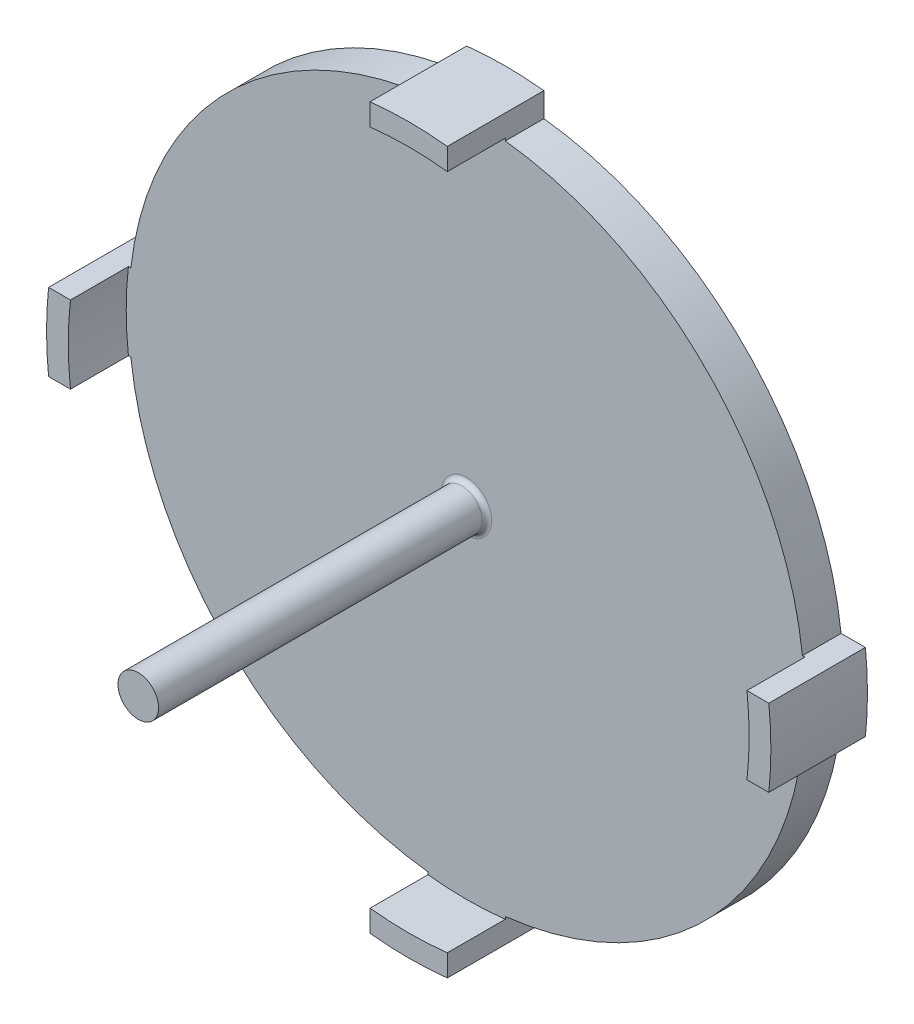
SolidWorks part; units mm, degrees
ref_plane "Front Plane" through (0, 0, 0) normal (0, 0, 1) x (1, 0, 0)
ref_plane "Top Plane" through (0, 0, 0) normal (0, 1, 0) x (1, 0, 0)
ref_plane "Right Plane" through (0, 0, 0) normal (1, 0, 0) x (0, 0, -1)
sketch "Sketch1" plane through (0, 0, 0) normal (0, 0, 1) x (1, 0, 0)
  line L0 (37.5, 4) -> (34.7707, 4)
  line L1 (-4, 37.5) -> (-4, 34.7707)
  line L2 (4, 37.5) -> (4, 34.7707)
  line L3 (4, -37.5) -> (4, -34.7707)
  line L4 (-37.5, -4) -> (-34.7707, -4)
  line L6 (4, 34.7707) -> (4, 37.5)
  line L8 (-34.7707, 4) -> (-37.5, 4)
  line L10 (-4, -34.7707) -> (-4, -37.5)
  line L12 (4, -34.7707) -> (4, -37.5)
  line L13 (34.7707, -4) -> (37.5, -4)
  circle A0 centre (0, 0) radius 35
  arc A1 (4, 35.0223) -> (-4, 35.0223) centre (0, 0) ccw
  arc A2 (-37.2861, 4) -> (-37.2861, -4) centre (0, 0) ccw
  arc A3 (-4, -37.2861) -> (4, -37.2861) centre (0, 0) ccw
  arc A4 (37.2861, -4) -> (37.2861, 4) centre (0, 0) ccw
  arc A5 (4, 37.2861) -> (-4, 37.2861) centre (0, 0) ccw
  arc A6 (-35.0223, 4) -> (-35.0223, -4) centre (0, 0) ccw
  arc A7 (35.0223, -4) -> (35.0223, 4) centre (0, 0) ccw
  arc A8 (-4, -35.0223) -> (4, -35.0223) centre (0, 0) ccw
  point P18 (0, 0)
  dimension "D1" = 70
  dimension "D2" = 70.5
  dimension "D3" = 75
  dimension "D4" = 4
extrude "Boss-Extrude1" add sketch "Sketch1" along normal blind 10 contours A6 L8 A2 L4 | L6 A5 L1 A1 | A7 L13 A4 L0 | A8 L10 A3 L12 region at (36.3014, 0, 0) region at (0, 36.3014, 0) region at (0, -36.3014, 0) region at (-36.3014, 0, 0)
extrude "Boss-Extrude2" add sketch "Sketch1<3>" along normal blind 4 contours A0 | L8 A6 L4 A0 | L10 A8 L3 A0 | L6 A1 L1 A0 | L13 A7 L0 A0 region at (35.0488, 0, 0) region at (0, 0, 0) region at (0, 35.0488, 0) region at (0, -35.0488, 0) region at (-35.0488, 0, 0)
sketch "Sketch1<3>" plane through (0, 0, 0) normal (0, 0, 1) x (1, 0, 0) same geometry as "Sketch1"
sketch "Sketch3" plane through (0, 0, 4) normal (0, 0, 1) x (1, 0, 0)
  circle A3 centre (0, 0) radius 2.1
  dimension "D1" = 4.2
extrude "Boss-Extrude3" add sketch "Sketch3" along normal blind 34
fillet "Fillet1" radius 0.5 1 edges at (2.1, 0, 4)
